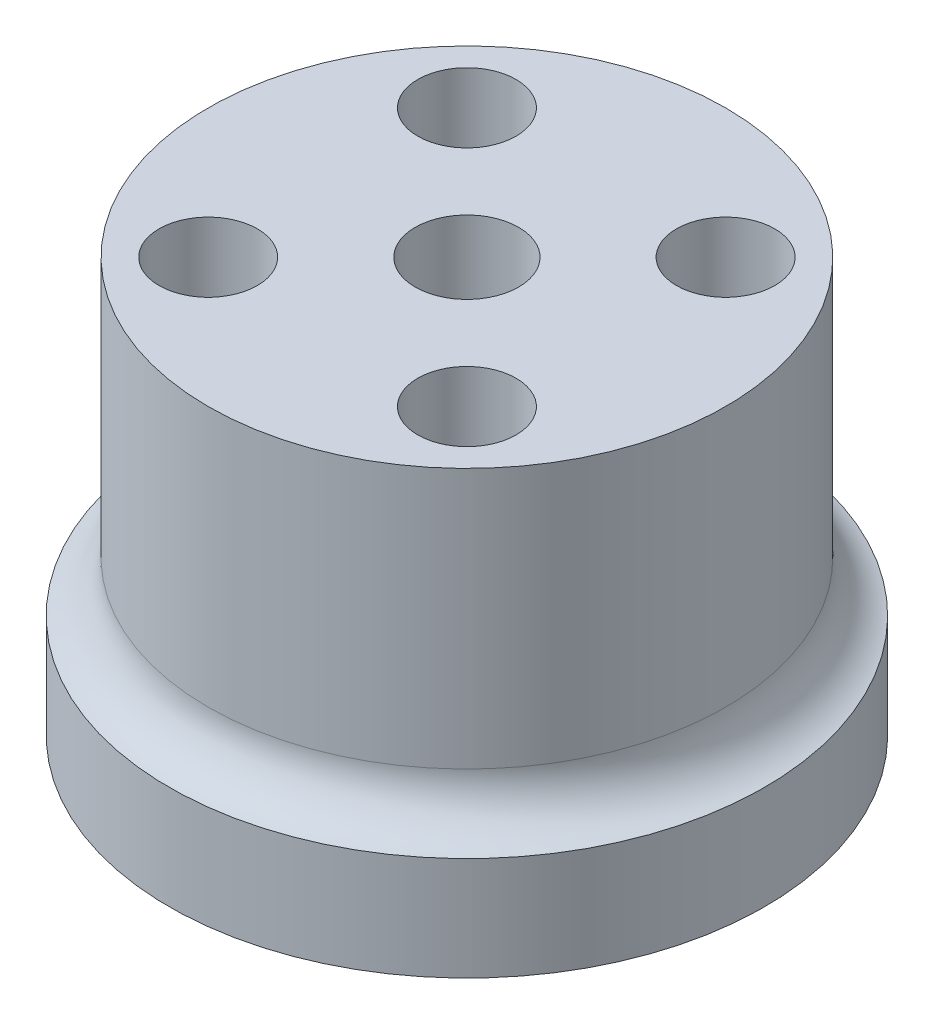
SolidWorks part; units mm, degrees
ref_plane "前视基准面" through (0, 0, 0) normal (0, 0, 1) x (1, 0, 0)
ref_plane "上视基准面" through (0, 0, 0) normal (0, 1, 0) x (1, 0, 0)
ref_plane "右视基准面" through (0, 0, 0) normal (1, 0, 0) x (0, 0, -1)
other "Configuration Table"
sketch "草图1" plane through (0, 0, 0) normal (0, 1, 0) x (1, 0, 0)
  line L1 (-5, -5) -> (5, -5)
  line L2 (-5, -5) -> (-5, 5)
  line L3 (-5, 5) -> (5, 5)
  line L4 (5, -5) -> (5, 5)
  line L5 (-5, -5) -> (5, 5) construction
  line L6 (-5, 5) -> (5, -5) construction
  circle A0 centre (0, 0) radius 10
  circle A1 centre (-5, 5) radius 1.9
  circle A2 centre (5, 5) radius 1.9
  circle A3 centre (5, -5) radius 1.9
  circle A4 centre (-5, -5) radius 1.9
  circle A5 centre (0, 0) radius 2
  point P17 (0, 0)
  dimension "D1" = 20
  dimension "D4" = 3.8
  dimension "D6" = 4
  dimension "D2" = 10
  dimension "D3" = 10
  dimension "D5" = 4
extrude "凸台-拉伸6" add sketch "草图1" along normal blind 20 contours A0 A4 L2 A1 L3 A2 L4 A3 L1 | A4 L1 A3 L4 A2 L3 A1 L2 A5 region at (-3.5565, 0, 3.5565) region at (-9.7172, 0, 0)
sketch "草图12" plane through (0, 0, 0) normal (0, -1, 0) x (1, 0, 0)
  circle A0 centre (0, 0) radius 3.1
  circle A1 centre (0, 0) radius 11.5
  dimension "D1" = 6.2
  dimension "D2" = 23
extrude "凸台-拉伸8" add sketch "草图12" against normal blind 4
sketch "草图13" plane through (0, 0, 0) normal (0, -1, 0) x (1, 0, 0)
  circle A0 centre (0, 0) radius 3
  dimension "D1" = 6
extrude "切除-拉伸7" cut sketch "草图13" against normal blind 2
fillet "圆角3" radius 2 1 edges at (0, 4, -10)
sketch "草图14" plane through (0, 20, 0) normal (0, 1, 0) x (1, 0, 0)
  circle A0 centre (0, 0) radius 10
  dimension "D1" = 20
extrude "切除-拉伸8" cut sketch "草图14" against normal blind 4
sketch "草图15" plane through (0, 0, 0) normal (0, -1, 0) x (1, 0, 0)
  circle A0 centre (0, 0) radius 3.25
  dimension "D1" = 6.5
extrude "切除-拉伸9" cut sketch "草图15" against normal blind 3
